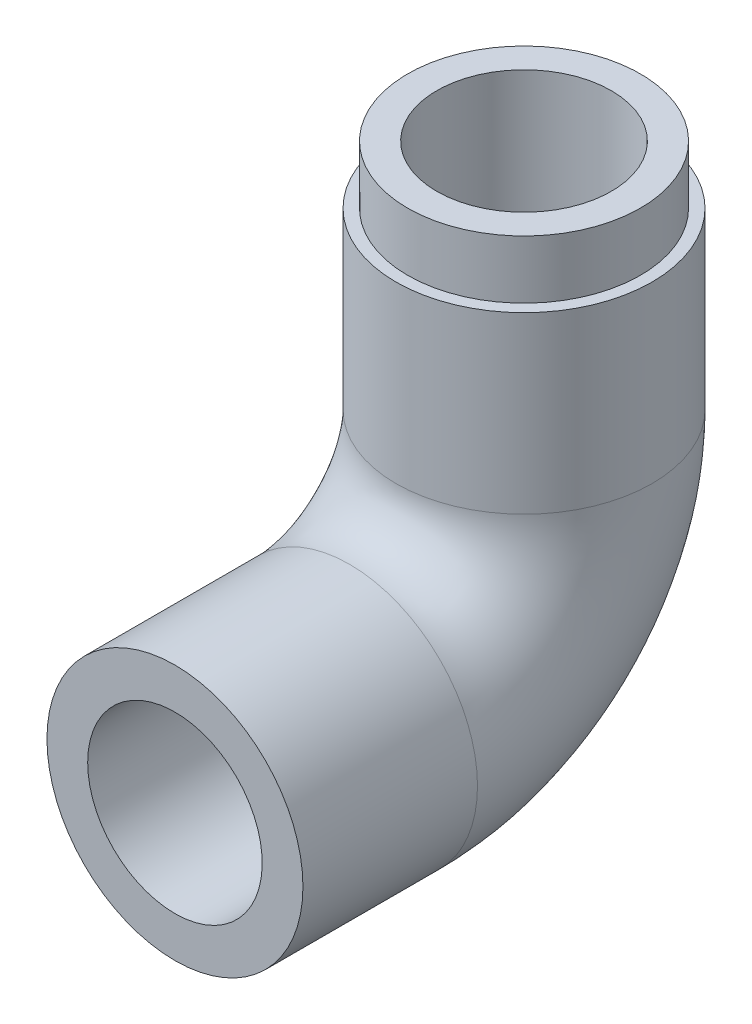
SolidWorks part; units mm, degrees
ref_plane "Front Plane" through (0, 0, 0) normal (0, 0, 1) x (1, 0, 0)
ref_plane "Top Plane" through (0, 0, 0) normal (0, 1, 0) x (1, 0, 0)
ref_plane "Right Plane" through (0, 0, 0) normal (1, 0, 0) x (0, 0, -1)
sketch "Sketch1" plane through (0, 0, 0) normal (1, 0, 0) x (0, 0, -1)
  line L0 (0, 0) -> (0, -15)
  line L1 (-15, -30) -> (-30, -30)
  arc A0 (0, -15) -> (-15, -30) centre (-15, -15) cw
  dimension "D1" = 15
  dimension "D2" = 15
  dimension "D3" = 15
sweep "Sweep1" add path "Sketch1" circular profile diameter 22 parameters "D3"=22
sweep "Cut-Sweep1" cut path "Sketch1<2>" circular profile diameter 15 parameters "D3"=15
sketch "Sketch1<2>" plane through (0, 0, 0) normal (1, 0, 0) x (0, 0, -1) same geometry as "Sketch1"
sketch "Sketch34" plane through (0, 0, 0) normal (0, 1, 0) x (1, 0, 0)
  circle A0 centre (0, 0) radius 7.5
  circle A1 centre (0, 0) radius 10
  dimension "D1" = 20
  dimension "D2" = 15
extrude "Boss-Extrude1" add sketch "Sketch34" along normal blind 5
